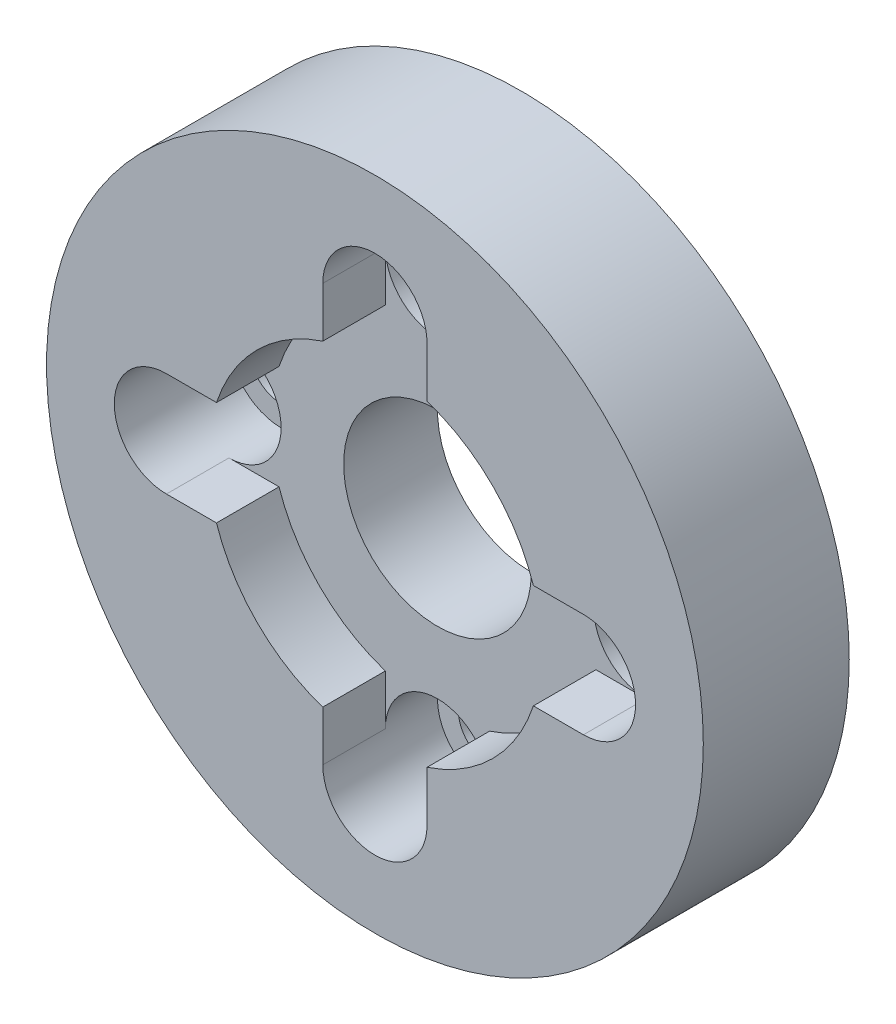
SolidWorks part; units mm, degrees
ref_plane "Front Plane" through (0, 0, 0) normal (0, 0, 1) x (1, 0, 0)
ref_plane "Top Plane" through (0, 0, 0) normal (0, 1, 0) x (1, 0, 0)
ref_plane "Right Plane" through (0, 0, 0) normal (1, 0, 0) x (0, 0, -1)
sketch "Sketch1" plane through (0, 0, 0) normal (0, 0, 1) x (1, 0, 0)
  circle A0 centre (0, 0) radius 31.5
  circle A1 centre (0, 0) radius 16
  circle A2 centre (0, 0) radius 9
  circle A3 centre (0, 0) radius 12.5
  dimension "D1" = 63
  dimension "D2" = 32
  dimension "D3" = 18
  dimension "D4" = 25
extrude "Boss-Extrude1" add sketch "Sketch1" along normal blind 14 contours A0 A1 region at (-30.609, 0, 0)
extrude "Boss-Extrude2" add sketch "Sketch1<3>" along normal blind 8 contours A1 A3 | A3 A2 region at (-15.5475, 0, 0) region at (-12.1464, 0, 0)
sketch "Sketch1<3>" plane through (0, 0, 0) normal (0, 0, 1) x (1, 0, 0) same geometry as "Sketch1"
extrude "Boss-Extrude3" add sketch "Sketch1<4>" against normal blind 1 contours A3 A2 region at (-12.1464, 0, 0)
sketch "Sketch1<4>" plane through (0, 0, 0) normal (0, 0, 1) x (1, 0, 0) same geometry as "Sketch1"
sketch "Sketch2" plane through (0, 0, 14) normal (0, 0, 1) x (1, 0, 0)
  line L0 (0, 0) -> (-31.5, 0) construction
  line L1 (0, 0) -> (0, 31.5) construction
  line L2 (-15, -5) -> (-15, 5)
  line L3 (-20, 5) -> (-15, 5)
  line L4 (-20, -5) -> (-15, -5)
  line L5 (20, -5) -> (15, -5)
  line L6 (15, -5) -> (15, 5)
  line L7 (20, 5) -> (15, 5)
  line L8 (-5, 20) -> (-5, 15)
  line L9 (5, 20) -> (5, 15)
  line L10 (-5, 15) -> (5, 15)
  line L11 (-5, -20) -> (-5, -15)
  line L12 (-5, -15) -> (5, -15)
  line L13 (5, -20) -> (5, -15)
  circle A0 centre (0, 0) radius 31.5 construction
  circle A2 centre (-20, 0) radius 5
  circle A3 centre (20, 0) radius 5
  circle A4 centre (0, 0) radius 16 construction
  circle A5 centre (0, 20) radius 5
  circle A6 centre (0, -20) radius 5
  circle A7 centre (-20, 0) radius 3
  circle A8 centre (0, 20) radius 3
  circle A9 centre (20, 0) radius 3
  circle A10 centre (0, -20) radius 3
  point P10 (-15, 0)
  circle M9 centre (0, 0) radius 16
  dimension "D2" = 10
  dimension "D3" = 10
  dimension "D6" = 6
  dimension "D7" = 6
  dimension "D1" = 15
  dimension "D4" = 15
  dimension "D5" = 5
extrude "Cut-Extrude1" cut sketch "Sketch2" against normal through all contours A7 | A8 | A9 | A10 region at (-20, 0, 14) region at (0, 20, 14) region at (20, 0, 14) region at (0, -20, 14)
extrude "Cut-Extrude2" cut sketch "Sketch2<3>" against normal up to surface (6 mm away) contours A2 L4 M9 | A2 L3 M9 | A5 L8 M9 | A5 L9 M9 | L11 A6 M9 | A6 L13 M9 | L5 A3 M9 | A3 L7 M9 region at (-16.5731, -4.3304, 14) region at (-16.5731, 4.3304, 14) region at (-4.3304, -16.5731, 14) region at (-4.3304, 16.5731, 14) region at (4.3304, -16.5731, 14) region at (4.3304, 16.5731, 14) region at (16.5731, -4.3304, 14) region at (16.5731, 4.3304, 14) up to face at (16, 0, 8)
sketch "Sketch2<3>" plane through (0, 0, 14) normal (0, 0, 1) x (1, 0, 0) same geometry as "Sketch2"
extrude "Cut-Extrude3" cut sketch "Sketch2<4>" against normal blind 11 contours A2 A7 M9 | A5 A8 M9 | A3 A9 M9 | A6 A10 M9 | A2 M9 | A5 M9 | A3 M9 | A6 M9 region at (-15.5523, 0, 14) region at (-16.1361, 0, 14) region at (-4.2608, -17.6541, 14) region at (0, -15.5523, 14) region at (0, 24.8639, 14) region at (0, 15.5523, 14) region at (17.6541, -4.2608, 14) region at (15.5523, 0, 14)
sketch "Sketch2<4>" plane through (0, 0, 14) normal (0, 0, 1) x (1, 0, 0) same geometry as "Sketch2"
